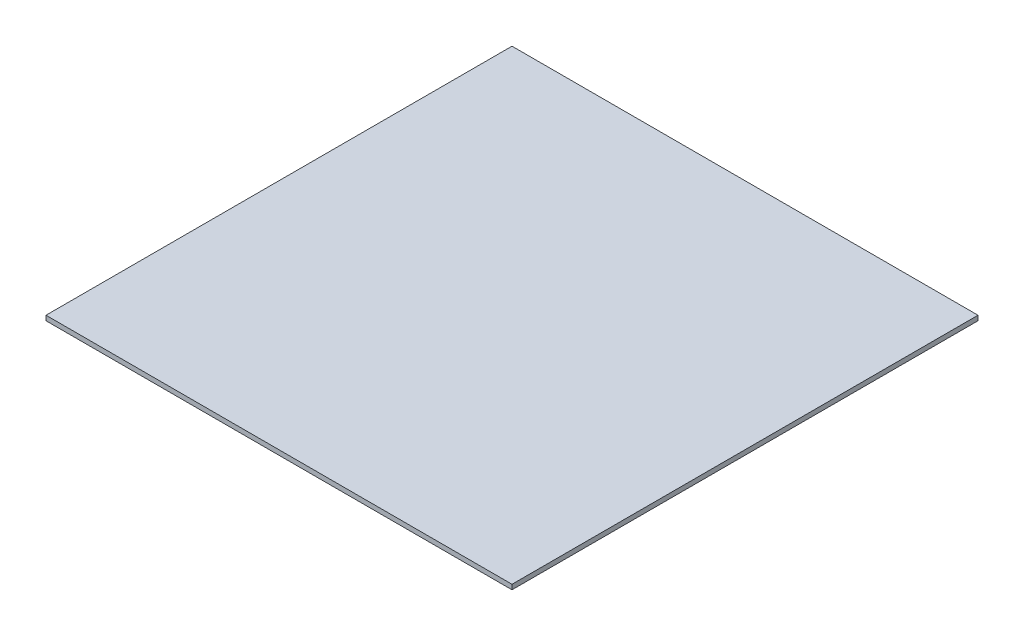
SolidWorks part; units mm, degrees
material "A-Glass Fiber"
ref_plane "Front Plane" through (0, 0, 0) normal (0, 0, 1) x (1, 0, 0)
ref_plane "Top Plane" through (0, 0, 0) normal (0, 1, 0) x (1, 0, 0)
ref_plane "Right Plane" through (0, 0, 0) normal (1, 0, 0) x (0, 0, -1)
sketch "Sketch1" plane through (0, 0, 0) normal (0, 1, 0) x (1, 0, 0)
  line L1 (-76.2, -76.2) -> (76.2, -76.2)
  line L2 (-76.2, -76.2) -> (-76.2, 76.2)
  line L3 (-76.2, 76.2) -> (76.2, 76.2)
  line L4 (76.2, -76.2) -> (76.2, 76.2)
  line L5 (-76.2, -76.2) -> (76.2, 76.2) construction
  line L6 (-76.2, 76.2) -> (76.2, -76.2) construction
  point P0 (0, 0)
  dimension "D1" = 152.4
  dimension "D2" = 152.4
extrude "Boss-Extrude1" add sketch "Sketch1" along normal blind 1.5748
